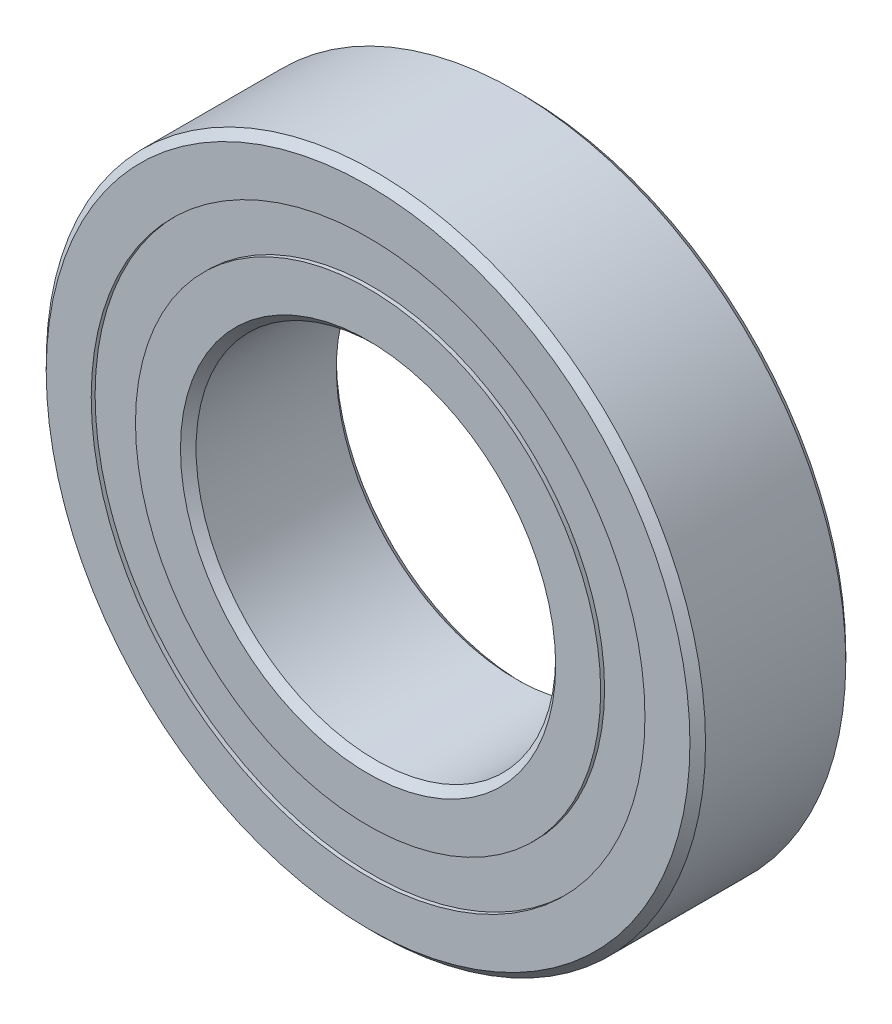
SolidWorks part; units mm, degrees
ref_plane "Front Plane" through (0, 0, 0) normal (0, 0, 1) x (1, 0, 0)
ref_plane "Top Plane" through (0, 0, 0) normal (0, 1, 0) x (1, 0, 0)
ref_plane "Right Plane" through (0, 0, 0) normal (1, 0, 0) x (0, 0, -1)
sketch "Sketch1" plane through (0, 0, 0) normal (1, 0, 0) x (0, 0, -1)
  line L0 (-6.5, 0) -> (6.5, 0) construction
  line L1 (0, 27.5) -> (0, -27.5) construction
  line L2 (5.85, 27.5) -> (-5.85, 27.5)
  line L3 (-5.85, 27.5) -> (-6.5, 26.85)
  line L4 (-6.5, 26.85) -> (-6.5, 23.0962)
  line L5 (-6.5, 23.0962) -> (-2.8889, 23.0962)
  line L6 (6.5, 23.0962) -> (2.8889, 23.0962)
  line L7 (6.5, 26.85) -> (6.5, 23.0962)
  line L8 (5.85, 27.5) -> (6.5, 26.85)
  line L9 (0, 27.5) -> (0, 21.25) construction
  line L10 (0, 21.25) -> (0, 15) construction
  arc A0 (-2.8889, 23.0962) -> (2.8889, 23.0962) centre (0, 21.25) cw
  point P14 (0, 15)
  dimension "Width" = 13
  dimension "OD" = 55
  dimension "D1" = 45
  dimension "D2" = 0.65
  dimension "Shaft Dia" = 30
  dimension "D3" = 5.7778
  dimension "D4" = 1.8462
revolve "Revolve1" add sketch "Sketch1" angle 360 about L0
sketch "Sketch3" plane through (0, 0, 0) normal (1, 0, 0) x (0, 0, -1)
  line L0 (-6.5, 19.4038) -> (-2.8889, 19.4038)
  line L1 (0, 27.5) -> (0, -27.5) construction
  line L2 (-6.5, 26.85) -> (-6.5, 23.0962) construction
  line L3 (-6.5, 19.4038) -> (-6.5, 15.65)
  line L4 (-5.85, 27.5) -> (-6.5, 26.85) construction
  line L5 (-6.5, 15.65) -> (-5.85, 15)
  line L6 (-5.85, 15) -> (5.85, 15)
  line L7 (5.85, 27.5) -> (5.85, -27.5) construction
  line L8 (5.85, 15) -> (6.5, 15.65)
  line L9 (6.5, -26.85) -> (6.5, 26.85) construction
  line L10 (6.5, 15.65) -> (6.5, 19.4038)
  line L11 (6.5, 19.4038) -> (2.8889, 19.4038)
  line L13 (5.85, 27.5) -> (6.5, 26.85) construction
  arc A0 (2.8889, 23.0962) -> (-2.8889, 23.0962) centre (0, 21.25) ccw construction
  arc A1 (2.8889, 19.4038) -> (-2.8889, 19.4038) centre (0, 21.25) cw
revolve "Revolve3" add sketch "Sketch3" angle 360 about L0
sketch "Sketch4" plane through (0, 0, 0) normal (1, 0, 0) x (0, 0, -1)
  line L0 (-3.4284, 21.25) -> (3.4284, 21.25)
  arc A2 (-3.4284, 21.25) -> (3.4284, 21.25) centre (0, 21.25) cw
  arc A3 (2.8889, 23.0962) -> (-2.8889, 23.0962) centre (0, 21.25) ccw construction
revolve "Revolve4" add sketch "Sketch4" angle 360 about L0
ref_axis "Axis1" through (0, 0, -6.5) along (0, 0, 1)
pattern_circular "CirPattern1" count 14 every 25.714 about axis through (0, 0, -6.5) along (0, 0, 1) of bodies 104
sketch "Sketch6" plane through (0, 0, 0) normal (1, 0, 0) x (0, 0, -1)
  line L0 (-6.5, 23.0962) -> (-2.8889, 23.0962) construction
  line L1 (-6.175, 23.0962) -> (-3.4284, 23.0962)
  line L2 (-6.175, 23.0962) -> (-6.175, 19.4038)
  line L3 (-6.175, 19.4038) -> (-3.4284, 19.4038)
  line L4 (-3.4284, 23.0962) -> (-3.4284, 19.4038)
  line L5 (-6.5, 19.4038) -> (-2.8889, 19.4038) construction
  line L6 (6.5, 23.0962) -> (2.8889, 23.0962) construction
  line L7 (6.175, 23.0962) -> (3.4284, 23.0962)
  line L8 (6.175, 23.0962) -> (6.175, 19.4038)
  line L9 (6.175, 19.4038) -> (3.4284, 19.4038)
  line L10 (3.4284, 23.0962) -> (3.4284, 19.4038)
  line L11 (6.5, 19.4038) -> (2.8889, 19.4038) construction
  line L12 (-5.85, 27.5) -> (-6.5, 26.85) construction
  point P18 (-6.175, 27.175)
revolve "Revolve5" add sketch "Sketch6" angle 360 about L0
sketch "Sketch7" plane through (0, 0, 6.5) normal (0, 0, 1) x (1, 0, 0)
  line L0 (0, 0) -> (0, -29.3986) construction
  circle A0 centre (0, 0) radius 15
  dimension "D1" = 30
equation "\"D2@Sketch1\" = \"Width@Sketch1\"*.05"
equation "\"D3@Sketch1\" = \"Width@Sketch1\"/2.25"
equation "\"D4@Sketch1\" = (((\"OD@Sketch1\"-\"Width@Sketch1\")/2)/3.25)/3.5"
equation "\"D2@CirPattern1\" = 360/\"Balls@CirPattern1\""
